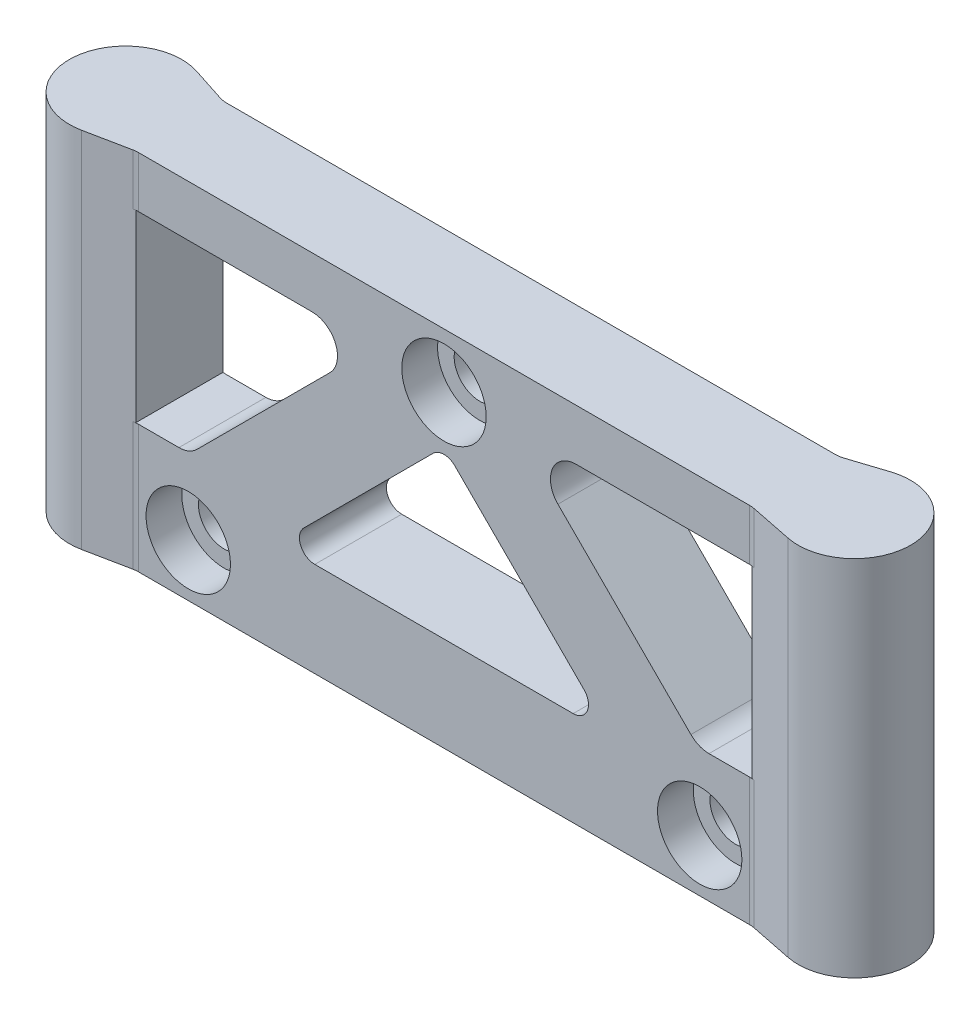
SolidWorks part; units mm, degrees
ref_plane "Front Plane" through (0, 0, 0) normal (0, 0, 1) x (1, 0, 0)
ref_plane "Top Plane" through (0, 0, 0) normal (0, 1, 0) x (1, 0, 0)
ref_plane "Right Plane" through (0, 0, 0) normal (1, 0, 0) x (0, 0, -1)
sketch "Sketch2" plane through (0, 0, 0) normal (0, 0, 1) x (1, 0, 0)
  line L0 (-100, 0) -> (0, 0) construction
  line L1 (-100, 10.25) -> (0, 10.25)
  line L2 (-100, -10.25) -> (0, -10.25)
  line L3 (0, 0) -> (-50, 50) construction
  line L4 (-7.2478, -7.2478) -> (-57.2478, 42.7522)
  line L5 (7.2478, 7.2478) -> (-42.7522, 57.2478)
  line L6 (-100, 0) -> (-50, 50) construction
  line L7 (-107.2478, 7.2478) -> (-57.2478, 57.2478)
  line L8 (-92.7522, -7.2478) -> (-42.7522, 42.7522)
  arc A0 (-100, 10.25) -> (-100, -10.25) centre (-100, 0) ccw
  arc A1 (0, -10.25) -> (0, 10.25) centre (0, 0) ccw
  arc A2 (-7.2478, -7.2478) -> (7.2478, 7.2478) centre (0, 0) ccw
  arc A3 (-42.7522, 57.2478) -> (-57.2478, 42.7522) centre (-50, 50) ccw
  arc A4 (-107.2478, 7.2478) -> (-92.7522, -7.2478) centre (-100, 0) ccw
  arc A5 (-42.7522, 42.7522) -> (-57.2478, 57.2478) centre (-50, 50) ccw
  point P3 (-50, 0)
  point P8 (-25, 25)
  point P15 (-75, 25)
  dimension "D1" = 100
  dimension "D2" = 20.5
  dimension "D3" = 45
  dimension "D4" = 45
extrude "Boss-Extrude4" add sketch "Sketch2" along normal blind 17 contours A4 L2 A2 L4 L1 L8 | A0 A4 L8 L1 | A3 L7 A0 L1 L8 L4 | L8 A5 A3 L4 | A5 L8 L4 L1 A1 L5 | L4 A2 A1 L1 region at (-74.0722, 27.272, 0) region at (-96.1173, 1.6083, 0) region at (-50, -1.0132, 0) region at (-25.9278, 27.272, 0) region at (-3.8827, 1.6083, 0) region at (-50, 49.2802, 0)
sketch "Sketch3" plane through (0, 0, 0) normal (0, 0, -1) x (-1, 0, 0)
  line L0 (57.2478, 57.2478) -> (107.2478, 7.2478)
  line L1 (57.2478, 57.2478) -> (107.2478, 7.2478)
  line L2 (100, -10.25) -> (0, -10.25)
  line L3 (100, -10.25) -> (0, -10.25)
  line L4 (-7.2478, 7.2478) -> (42.7522, 57.2478)
  line L5 (-7.2478, 7.2478) -> (42.7522, 57.2478)
  circle A0 centre (0, 0) radius 8.25
  circle A1 centre (50, 50) radius 8.25
  circle A2 centre (100, 0) radius 8.25
  arc A3 (100, -10.25) -> (107.2478, 7.2478) centre (100, 0) ccw
  arc A4 (100, -10.25) -> (107.2478, 7.2478) centre (100, 0) ccw
  arc A5 (-7.2478, 7.2478) -> (0, -10.25) centre (0, 0) ccw
  arc A6 (-7.2478, 7.2478) -> (0, -10.25) centre (0, 0) ccw
  arc A7 (57.2478, 57.2478) -> (42.7522, 57.2478) centre (50, 50) ccw
  arc A8 (57.2478, 57.2478) -> (42.7522, 57.2478) centre (50, 50) ccw
  dimension "D1" = 16.5
  dimension "D2" = 16.5
  dimension "D3" = 16.5
extrude "Cut-Extrude1" cut sketch "Sketch3" against normal blind 7 contours A0 | A1 | A2 region at (0, 0, 0) region at (-50, 50, 0) region at (-100, 0, 0)
sketch "Sketch4" plane through (0, 0, 17) normal (0, 0, 1) x (1, 0, 0)
  circle A0 centre (-100, 0) radius 8.25
  circle A1 centre (-50, 50) radius 8.25
  circle A2 centre (0, 0) radius 8.25
  arc A3 (-107.2478, 7.2478) -> (-100, -10.25) centre (-100, 0) ccw construction
  arc A4 (-42.7522, 57.2478) -> (-57.2478, 57.2478) centre (-50, 50) ccw construction
  arc A5 (0, -10.25) -> (7.2478, 7.2478) centre (0, 0) ccw construction
  dimension "D1" = 16.5
  dimension "D2" = 16.5
  dimension "D3" = 16.5
extrude "Cut-Extrude2" cut sketch "Sketch4" against normal blind 7
sketch "Sketch5" plane through (0, 0, 0) normal (0, 0, -1) x (-1, 0, 0)
  line L2 (17.5, 8.25) -> (50, 40.75)
  line L3 (50, 40.75) -> (82.5, 8.25)
  line L4 (82.5, 8.25) -> (17.5, 8.25)
  circle A0 centre (0, 0) radius 8.25 construction
  circle A2 centre (50, 50) radius 8.25 construction
  dimension "D3" = 45
  dimension "D1" = 9.25
  dimension "D2" = 45
extrude "Cut-Extrude3" cut sketch "Sketch5" against normal through all
sketch "Sketch6" plane through (0, 0, 17) normal (0, 0, 1) x (1, 0, 0)
  circle A1 centre (-100, 0) radius 5
  circle A2 centre (-50, 50) radius 5
  circle A3 centre (0, 0) radius 5
  circle A4 centre (-100, 0) radius 8.25 construction
  circle A6 centre (-50, 50) radius 8.25 construction
  circle A7 centre (0, 0) radius 8.25 construction
  dimension "D1" = 10
  dimension "D2" = 10
  dimension "D3" = 10
extrude "Cut-Extrude4" cut sketch "Sketch6" against normal blind 16.6
fillet "Fillet1" radius 3 3 edges at (-82.5, 8.25, 8.5) (-17.5, 8.25, 8.5) (-50, 40.75, 8.5)
sketch "Sketch7" plane through (0, 0, 0) normal (0, 0, -1) x (-1, 0, 0)
  line L0 (0, -10.25) -> (-10.25, -10.25)
  line L1 (-10.25, -10.25) -> (-10.25, 14.75)
  line L2 (-10.25, 14.75) -> (0.2543, 14.75)
  line L3 (-7.2478, 7.2478) -> (42.7522, 57.2478) construction
  line L7 (42.7522, 57.2478) -> (-7.2478, 7.2478)
  line L8 (0, -10.25) -> (100, -10.25)
  line L9 (107.2478, 7.2478) -> (57.2478, 57.2478)
  line L10 (42.7522, 57.2478) -> (-7.2478, 7.2478)
  line L11 (0, -10.25) -> (100, -10.25)
  line L12 (107.2478, 7.2478) -> (57.2478, 57.2478)
  arc A0 (-7.2478, 7.2478) -> (0, -10.25) centre (0, 0) ccw construction
  arc A4 (-7.2478, 7.2478) -> (0, -10.25) centre (0, 0) ccw
  arc A5 (100, -10.25) -> (107.2478, 7.2478) centre (100, 0) ccw
  arc A6 (57.2478, 57.2478) -> (42.7522, 57.2478) centre (50, 50) ccw
  arc A7 (-7.2478, 7.2478) -> (0, -10.25) centre (0, 0) ccw
  arc A8 (100, -10.25) -> (107.2478, 7.2478) centre (100, 0) ccw
  arc A9 (57.2478, 57.2478) -> (42.7522, 57.2478) centre (50, 50) ccw
  line M13 (42.7522, 57.2478) -> (-7.2478, 7.2478)
  arc M14 (-7.2478, 7.2478) -> (0, -10.25) centre (0, 0) ccw
  dimension "D1" = 25
  dimension "D2" = 0
extrude "Boss-Extrude5" add sketch "Sketch7" against normal blind 17 contours L2 L1 M14 M13 | L1 L0 M14 region at (7.9605, -7.9605, 0) region at (6.8621, 10.9629, 0)
sketch "Sketch8" plane through (0, 14.75, 0) normal (0, 1, 0) x (1, 0, 0)
  line L0 (10.25, -17) -> (10.25, 0) construction
  line L1 (10.25, -17) -> (-0.2543, -17) construction
  line L2 (10.25, -17) -> (19.0718, -18.7822)
  line L3 (10.25, 0) -> (17.8608, 2.4649)
  line L4 (10.25, 0) -> (10.25, -17)
  circle A0 centre (21.25, -8) radius 8.25
  circle A1 centre (21.25, -8) radius 11
  line M4 (10.25, -17) -> (10.25, 0)
  dimension "D1" = 16.5
  dimension "D2" = 22
  dimension "D3" = 9
extrude "Boss-Extrude6" add sketch "Sketch8" against normal blind 25 and the other way blind 46 contours A1 L3 L4 | A1 A0 | A1 L2 M4 region at (12.1677, 14.75, 15.431) region at (12.9773, 14.75, 14.7686) region at (11.882, 14.75, 1.1869)
sketch "Sketch9" plane through (10.25, 0, 0) normal (-1, 0, 0) x (0, 0, 1)
  line L1 (0, 60.75) -> (17, 60.75)
  line L2 (0, 60.75) -> (0, 50.75)
  line L3 (0, 50.75) -> (17, 50.75)
  line L4 (17, 60.75) -> (17, 50.75)
  line L5 (17, 60.75) -> (17, 14.75) construction
  line L6 (0, 60.75) -> (0, 14.75) construction
  line L7 (17, 60.75) -> (0, 60.75) construction
  dimension "D1" = 10
extrude "Boss-Extrude7" add sketch "Sketch9" along normal up to surface (56.5043 mm away) up to face at (-21.5032, 35.9989, 8.5)
fillet "Fillet2" radius 5 4 edges at (10.25, 2.25, 0) (10.25, 55.75, 0) (10.25, 55.75, 17) (10.25, 2.25, 17)
fillet "Fillet5" radius 5 2 edges at (-36.2543, 50.75, 8.5) (-0.2543, 14.75, 8.5)
sketch "Sketch10" plane through (0, 0, 0) normal (0, 0, -1) x (-1, 0, 0)
  line L0 (100, -10.25) -> (-9.4605, -10.25) construction
  line L1 (110.25, -10.25) -> (50, -10.25)
  line L2 (110.25, -10.25) -> (110.25, 60.25)
  line L3 (110.25, 60.25) -> (50, 60.25)
  line L4 (50, -10.25) -> (50, 60.25)
  arc A0 (57.2478, 57.2478) -> (42.7522, 57.2478) centre (50, 50) ccw construction
  arc A1 (100, -10.25) -> (107.2478, 7.2478) centre (100, 0) ccw construction
  point P8 (112.8433, -12.1427)
extrude "Cut-Extrude5" cut sketch "Sketch10" against normal through all
mirror "Mirror1" about plane through (-50, -10.25, 19) normal (1, 0, 0) of bodies 110
sketch "Sketch11" plane through (0, 0, 0) normal (0, 0, -1) x (-1, 0, 0)
  line L0 (46.2543, 60.75) -> (53.7457, 60.75)
  line L15 (-9.4605, -10.25) -> (109.4605, -10.25)
  line L16 (109.4605, -10.25) -> (109.4605, 14.75)
  line L17 (109.4605, 14.75) -> (101.8168, 14.75)
  line L18 (98.2812, 16.2145) -> (72.2812, 42.2145)
  line L19 (75.8168, 50.75) -> (109.4605, 50.75)
  line L20 (109.4605, 50.75) -> (109.4605, 60.75)
  line L21 (109.4605, 60.75) -> (53.7457, 60.75)
  line L22 (53.7457, 60.75) -> (57.2478, 57.2478)
  line L23 (42.7522, 57.2478) -> (46.2543, 60.75)
  line L24 (46.2543, 60.75) -> (-9.4605, 60.75)
  line L25 (-9.4605, 60.75) -> (-9.4605, 50.75)
  line L26 (-9.4605, 50.75) -> (24.1832, 50.75)
  line L27 (27.7188, 42.2145) -> (1.7188, 16.2145)
  line L28 (-1.8168, 14.75) -> (-9.4605, 14.75)
  line L29 (-9.4605, 14.75) -> (-9.4605, -10.25)
  line L30 (-9.4605, -10.25) -> (109.4605, -10.25)
  line L31 (109.4605, -10.25) -> (109.4605, 14.75)
  line L32 (109.4605, 14.75) -> (101.8168, 14.75)
  line L33 (98.2812, 16.2145) -> (72.2812, 42.2145)
  line L34 (75.8168, 50.75) -> (109.4605, 50.75)
  line L35 (109.4605, 50.75) -> (109.4605, 60.75)
  line L36 (109.4605, 60.75) -> (53.7457, 60.75)
  line L37 (53.7457, 60.75) -> (57.2478, 57.2478)
  line L38 (42.7522, 57.2478) -> (46.2543, 60.75)
  line L39 (46.2543, 60.75) -> (-9.4605, 60.75)
  line L40 (-9.4605, 60.75) -> (-9.4605, 50.75)
  line L41 (-9.4605, 50.75) -> (24.1832, 50.75)
  line L42 (27.7188, 42.2145) -> (1.7188, 16.2145)
  line L43 (-1.8168, 14.75) -> (-9.4605, 14.75)
  line L44 (-9.4605, 14.75) -> (-9.4605, -10.25)
  arc A5 (98.2812, 16.2145) -> (101.8168, 14.75) centre (101.8168, 19.75) ccw
  arc A6 (75.8168, 50.75) -> (72.2812, 42.2145) centre (75.8168, 45.75) ccw
  arc A7 (57.2478, 57.2478) -> (42.7522, 57.2478) centre (50, 50) ccw
  arc A8 (27.7188, 42.2145) -> (24.1832, 50.75) centre (24.1832, 45.75) ccw
  arc A9 (-1.8168, 14.75) -> (1.7188, 16.2145) centre (-1.8168, 19.75) ccw
  arc A10 (98.2812, 16.2145) -> (101.8168, 14.75) centre (101.8168, 19.75) ccw
  arc A11 (75.8168, 50.75) -> (72.2812, 42.2145) centre (75.8168, 45.75) ccw
  arc A12 (57.2478, 57.2478) -> (42.7522, 57.2478) centre (50, 50) ccw
  arc A13 (27.7188, 42.2145) -> (24.1832, 50.75) centre (24.1832, 45.75) ccw
  arc A14 (-1.8168, 14.75) -> (1.7188, 16.2145) centre (-1.8168, 19.75) ccw
  line M37 (53.7457, 60.75) -> (57.2478, 57.2478)
  arc M38 (57.2478, 57.2478) -> (42.7522, 57.2478) centre (50, 50) ccw
  line M39 (42.7522, 57.2478) -> (46.2543, 60.75)
  dimension "D1" = 0
extrude "Boss-Extrude8" add sketch "Sketch11" against normal blind 17 contours L0 M39 M38 M37 region at (-50, 60.6009, 0)
sketch "Sketch12" plane through (0, 60.75, 0) normal (0, 1, 0) x (1, 0, 0)
  circle A0 centre (-121.25, -8) radius 11
  circle A1 centre (21.25, -8) radius 11
  arc A2 (19.0718, -18.7822) -> (17.8608, 2.4649) centre (21.25, -8) ccw construction
  arc A3 (-117.8608, 2.4649) -> (-119.0718, -18.7822) centre (-121.25, -8) ccw construction
extrude "Boss-Extrude9" add sketch "Sketch12" against normal blind 20
equation "\"D4@Sketch2\"=\"D3@Sketch2\""
equation "\"D2@Sketch3\"=\"D1@Sketch3\""
equation "\"D3@Sketch3\"=\"D1@Sketch3\""
equation "\"D2@Sketch4\"=\"D1@Sketch4\""
equation "\"D3@Sketch4\"=\"D1@Sketch4\""
equation "\"D3@Sketch5\"=\"D2@Sketch5\""
equation "\"D2@Sketch6\"=\"D1@Sketch6\""
equation "\"D3@Sketch6\"=\"D2@Sketch6\""
